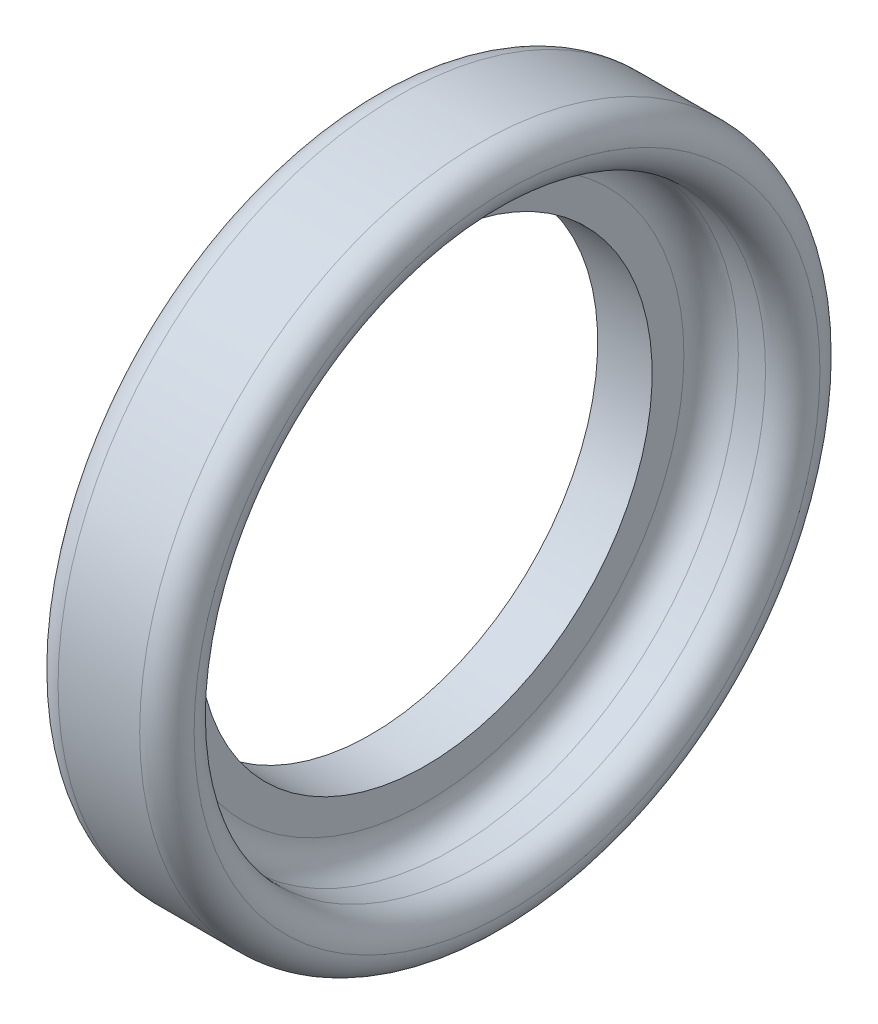
SolidWorks part; units mm, degrees
ref_plane "Front Plane" through (0, 0, 0) normal (0, 0, 1) x (1, 0, 0)
ref_plane "Top Plane" through (0, 0, 0) normal (0, 1, 0) x (1, 0, 0)
ref_plane "Right Plane" through (0, 0, 0) normal (1, 0, 0) x (0, 0, -1)
sketch "Sketch1" plane through (0, 0, 0) normal (0, 0, 1) x (1, 0, 0)
  line L0 (15, 31.5) -> (15, 37.5)
  line L1 (15, 37.5) -> (0, 37.5)
  line L2 (0, 37.5) -> (0, 25)
  line L3 (0, 25) -> (6, 25)
  line L4 (6, 25) -> (6, 31.5)
  line L5 (6, 31.5) -> (15, 31.5)
  line L6 (0, 0) -> (38.3081, 0) construction
  dimension "D1" = 15
  dimension "D2" = 37.5
  dimension "D3" = 6
  dimension "D4" = 6
  dimension "D5" = 25
revolve "Revolve1" add sketch "Sketch1" angle 360 about L6
fillet "Fillet1" radius 3 2 edges at (15, 0, 31.5) (15, 0, 37.5)
fillet "Fillet2" radius 3 2 edges at (6, 0, 31.5) (0, 0, 37.5)
